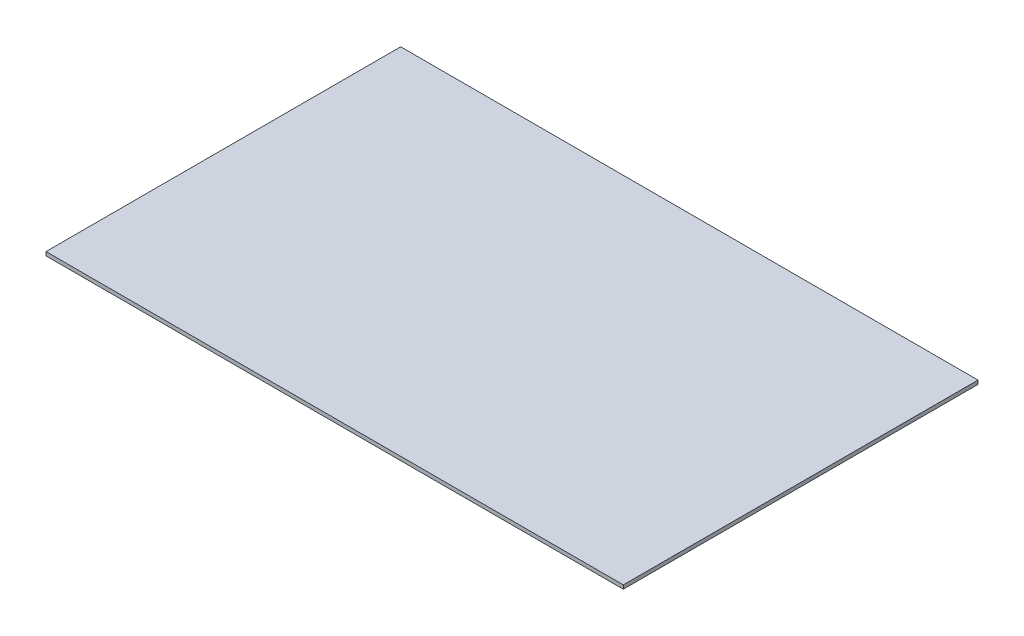
SolidWorks part; units mm, degrees
material "Бальса"
ref_plane "Спереди" through (0, 0, 0) normal (0, 0, 1) x (1, 0, 0)
ref_plane "Сверху" through (0, 0, 0) normal (0, 1, 0) x (1, 0, 0)
ref_plane "Справа" through (0, 0, 0) normal (1, 0, 0) x (0, 0, -1)
sketch "Эскиз1" plane through (0, 0, 0) normal (0, 1, 0) x (1, 0, 0)
  line L1 (0, 0) -> (1530, 0)
  line L2 (0, 0) -> (0, 940)
  line L3 (0, 940) -> (1530, 940)
  line L4 (1530, 0) -> (1530, 940)
  dimension "D1" = 940
  dimension "D2" = 1530
extrude "Бобышка-Вытянуть1" add sketch "Эскиз1" along normal blind 10
